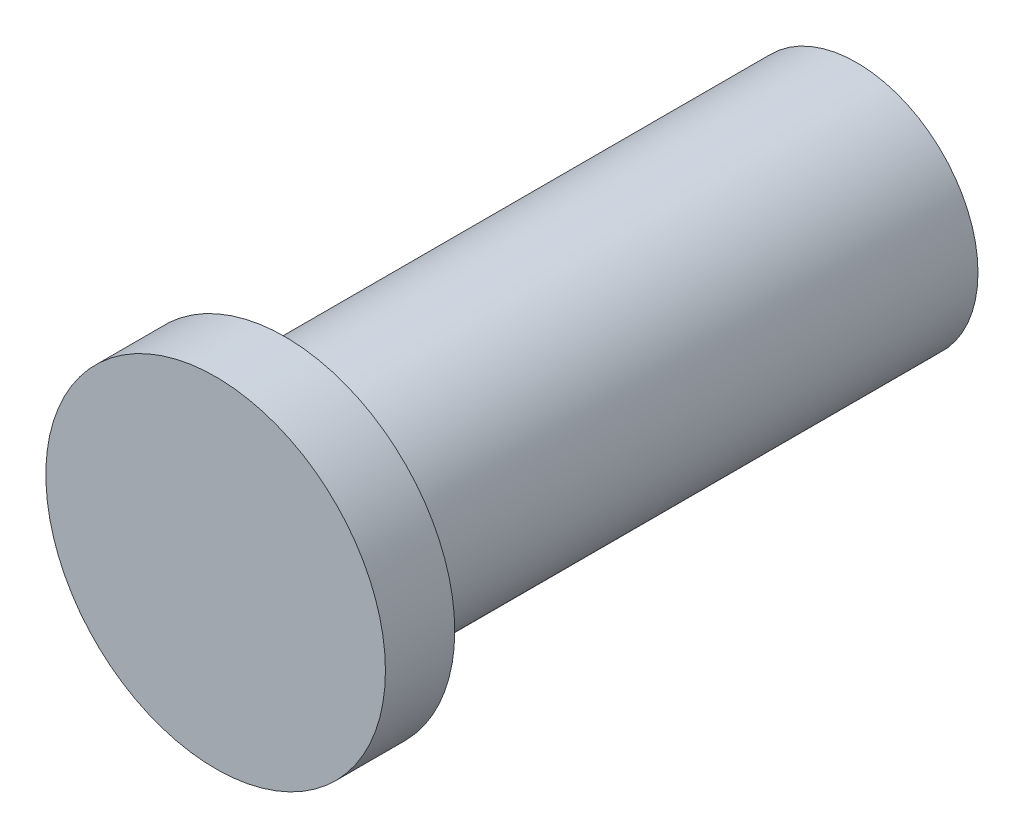
SolidWorks part; units mm, degrees
ref_plane "Front Plane" through (0, 0, 0) normal (0, 0, 1) x (1, 0, 0)
ref_plane "Top Plane" through (0, 0, 0) normal (0, 1, 0) x (1, 0, 0)
ref_plane "Right Plane" through (0, 0, 0) normal (1, 0, 0) x (0, 0, -1)
sketch "Sketch1" plane through (0, 0, 0) normal (0, 0, 1) x (1, 0, 0)
  circle A0 centre (0, 0) radius 7
  dimension "D1" = 14
extrude "Boss-Extrude1" add sketch "Sketch1" along normal blind 33
sketch "Sketch2" plane through (0, 0, 33) normal (0, 0, 1) x (1, 0, 0)
  circle A0 centre (0, 0) radius 9.8
  dimension "D1" = 19.6
extrude "Boss-Extrude2" add sketch "Sketch2" along normal blind 4
sketch "Sketch3" plane through (0, 0, 0) normal (0, 0, -1) x (-1, 0, 0)
  circle A0 centre (0, 0) radius 4.2
  dimension "D1" = 8.4
extrude "Cut-Extrude1" cut sketch "Sketch3" against normal blind 15
thread "Thread1" pitch 1 method cut profile "Thread Profile1" start angle 0, offset 0, length 0, pitch 1, diameter 8.4
ref_plane "Plane2" through (-4.2, 0, 15) normal (0, -1, 0) x (-1, 0, 0)
sketch "Thread Profile1" plane through (-4.2, 0, 15) normal (0, -1, 0) x (-1, 0, 0)
  line L0 (0, 0) -> (0, 1) construction
  line L1 (0, 0) -> (0.5413, 0.3125)
  line L2 (0.5413, 0.3125) -> (0.5413, 0.4375)
  line L3 (0.5413, 0.4375) -> (0, 0.75)
  line L4 (0.5413, 0.375) -> (0, 0.375) construction
  line L11 (0, 0) -> (0, 0.75)
  point P2 (0, 0)
  dimension "Pitch" = 1
  dimension "Profile_Angle" = 60
  dimension "Profile_Land" = 0.125
  dimension "Profile_Height" = 0.5413
equation "\"pin_diameter\"=14.00"
equation "\"upper_pin_length\"=63.00"
equation "\"lower_pin_length\"=33.00"
equation "\"D1@Sketch1\"=\"pin_diameter\""
equation "\"D1@Boss-Extrude1\"=\"lower_pin_length\""
equation "\"pin_head_diameter\"=19.60"
equation "\"D1@Sketch2\"=\"pin_head_diameter\""
equation "\"pin_screw_diameter\"=8.40"
equation "\"D1@Sketch3\"=\"pin_screw_diameter\""
